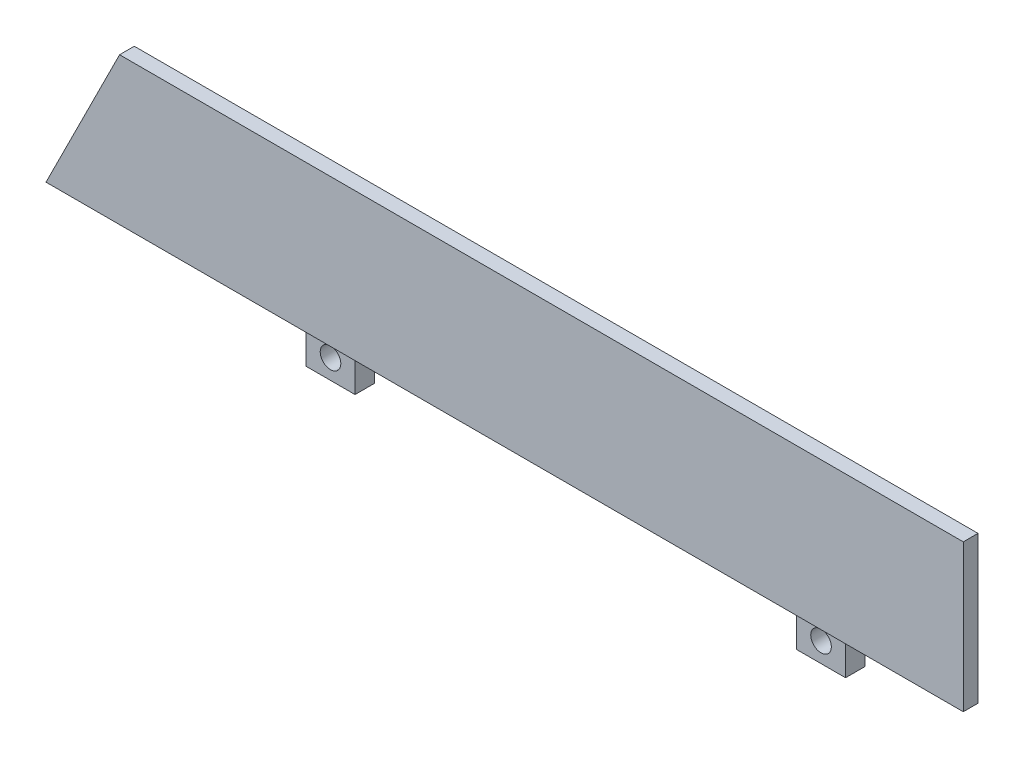
SolidWorks part; units mm, degrees
material "ABS"
ref_plane "Płaszczyzna przednia" through (0, 0, 0) normal (0, 0, 1) x (1, 0, 0)
ref_plane "Płaszczyzna górna" through (0, 0, 0) normal (0, 1, 0) x (1, 0, 0)
ref_plane "Płaszczyzna prawa" through (0, 0, 0) normal (1, 0, 0) x (0, 0, -1)
sketch "Szkic1" plane through (0, 0, 0) normal (0, 0, 1) x (1, 0, 0)
  line L0 (0, 0) -> (187, 0)
  line L1 (187, 0) -> (187, 30)
  line L2 (187, 30) -> (15, 30)
  line L3 (15, 30) -> (0, 0)
  dimension "D1" = 187
  dimension "D2" = 30
  dimension "D3" = 172
extrude "Dodanie-wyciągnięcie1" add sketch "Szkic1" along normal blind 3
sketch "Szkic2" plane through (0, 0, 0) normal (0, 0, -1) x (-1, 0, 0)
  line L0 (-187, 0) -> (-187, 30) construction
  line L1 (0, 0) -> (-187, 0) construction
  line L3 (-160, 5) -> (-150, 5)
  line L4 (-160, 5) -> (-160, -9)
  line L5 (-160, -9) -> (-150, -9)
  line L6 (-150, 5) -> (-150, -9)
  circle A0 centre (-155, -5) radius 2.1
  point P11 (-155, -9)
  dimension "D5" = 4.2
  dimension "D1" = 32
  dimension "D2" = 4
  dimension "D3" = 10
  dimension "D4" = 9
  dimension "D6" = 14
extrude "Dodanie-wyciągnięcie2" add sketch "Szkic2" along normal blind 4
chamfer "Sfazowanie1" distance 4 angle 45 3 edges at (160, 2.5, 0) (155, 5, 0) (150, 2.5, 0)
pattern_linear "Szyk liniowy1" count 2 spacing 100 along (-1, 0, 0) of "Sfazowanie1", "Dodanie-wyciągnięcie2"
